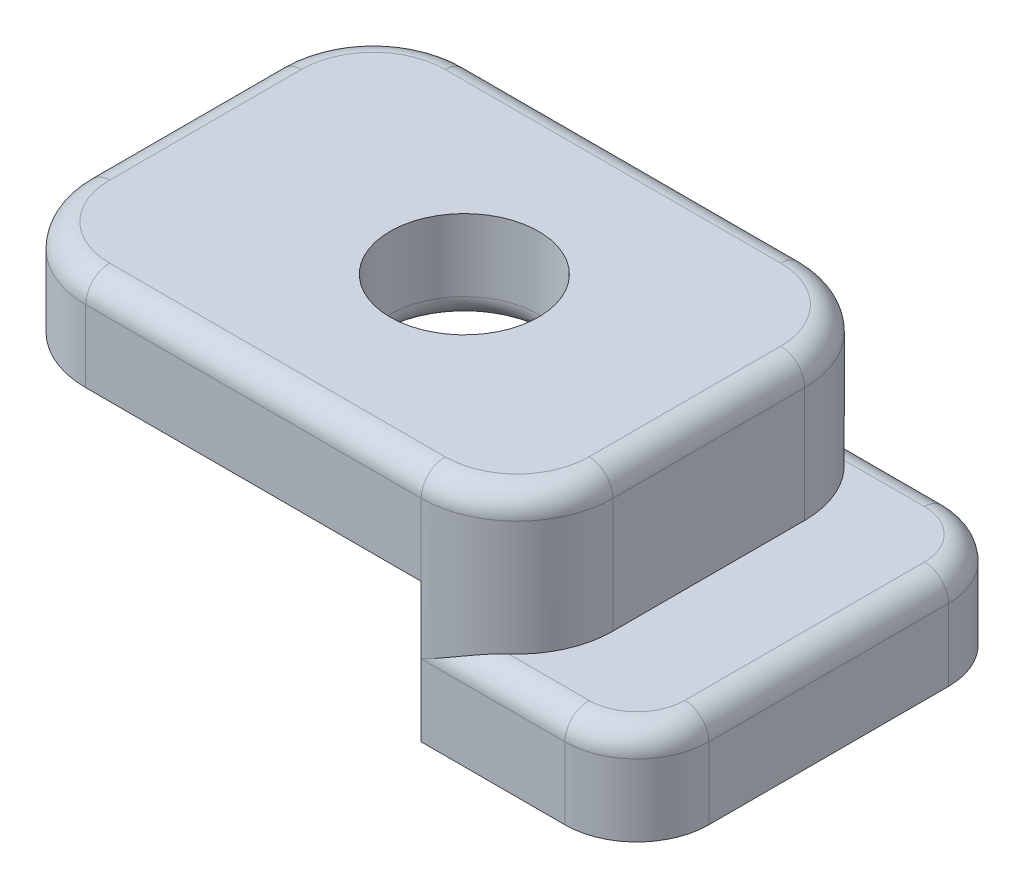
SolidWorks part; units mm, degrees
ref_plane "Front Plane" through (0, 0, 0) normal (0, 0, 1) x (1, 0, 0)
ref_plane "Top Plane" through (0, 0, 0) normal (0, 1, 0) x (1, 0, 0)
ref_plane "Right Plane" through (0, 0, 0) normal (1, 0, 0) x (0, 0, -1)
sketch "Sketch1" plane through (0, 0, 0) normal (0, 1, 0) x (1, 0, 0)
  line L1 (3.5, 4) -> (-3.5, 4)
  line L2 (5.5, 2) -> (5.5, -2)
  line L3 (3.5, -4) -> (-3.5, -4)
  line L4 (-5.5, 2) -> (-5.5, -2)
  line L5 (5.5, 4) -> (-5.5, -4) construction
  line L6 (5.5, -4) -> (-5.5, 4) construction
  arc A1 (-3.5, 4) -> (-5.5, 2) centre (-3.5, 2) ccw
  arc A2 (-3.5, -4) -> (-5.5, -2) centre (-3.5, -2) cw
  arc A3 (5.5, -2) -> (3.5, -4) centre (3.5, -2) cw
  arc A4 (3.5, 4) -> (5.5, 2) centre (3.5, 2) cw
  point P0 (0, 0)
  dimension "D1" = 2
  dimension "D2" = 11
  dimension "D3" = 8
extrude "Boss-Extrude1" add sketch "Sketch1" along normal blind 2
sketch "Sketch2" plane through (0, 2, 0) normal (0, 1, 0) x (1, 0, 0)
  line L0 (5.5, -2) -> (5.5, 2) construction
  line L2 (5.5, 0) -> (-5.5, 0) construction
  line L3 (-5.5, 2) -> (-5.5, -2) construction
  circle A0 centre (0.4, 0) radius 1.55
  point P4 (0, 0)
  dimension "D1" = 3.1
  dimension "D2" = 5.1
extrude "Cut-Extrude1" cut sketch "Sketch2" against normal through all both and the other way through all
sketch "Sketch3" plane through (0, 0, 0) normal (0, -1, 0) x (1, 0, 0)
  line L1 (5.5, 2) -> (5.5, -2) construction
  line L4 (5.5, 2) -> (5.5, -2)
  line L6 (3.5, 4) -> (3.5, -4)
  arc A0 (3.5, -4) -> (5.5, -2) centre (3.5, -2) ccw construction
  arc A1 (5.5, 2) -> (3.5, 4) centre (3.5, 2) ccw construction
  arc A2 (3.5, -4) -> (5.5, -2) centre (3.5, -2) ccw
  arc A3 (5.5, 2) -> (3.5, 4) centre (3.5, 2) ccw
  dimension "D1" = 2
extrude "Boss-Extrude2" add sketch "Sketch3" along normal blind 2.9
sketch "Sketch4" plane through (0, -2.9, 0) normal (0, -1, 0) x (1, 0, 0)
  line L0 (5.5, 2) -> (5.5, -2) construction
  line L1 (5.5, 2) -> (5.5, -2)
  line L2 (3.5, 4) -> (6.5, 4)
  line L3 (8, 2.5) -> (8, -2.5)
  line L4 (6.5, -4) -> (3.5, -4)
  arc A0 (3.5, -4) -> (5.5, -2) centre (3.5, -2) ccw construction
  arc A1 (5.5, 2) -> (3.5, 4) centre (3.5, 2) ccw construction
  arc A2 (3.5, -4) -> (5.5, -2) centre (3.5, -2) ccw
  arc A3 (5.5, 2) -> (3.5, 4) centre (3.5, 2) ccw
  arc A4 (6.5, 4) -> (8, 2.5) centre (6.5, 2.5) cw
  arc A5 (8, -2.5) -> (6.5, -4) centre (6.5, -2.5) cw
  dimension "D1" = 1.5
  dimension "D2" = 2.5
extrude "Boss-Extrude3" add sketch "Sketch4" against normal blind 2
fillet "Fillet1" radius 0.5 14 edges at (4.9142, 2, 3.4142) (0, 2, 4) (-4.9142, 2, 3.4142) (-5.5, 2, 0) (-4.9142, 2, -3.4142) (0, 2, -4) (4.9142, 2, -3.4142) (5, -0.9, -4) (7.5607, -0.9, -3.5607) (5, -0.9, 4) (7.5607, -0.9, 3.5607) (0.4, 0, 1.55) (5.5, 2, 0) (8, -0.9, 0)
